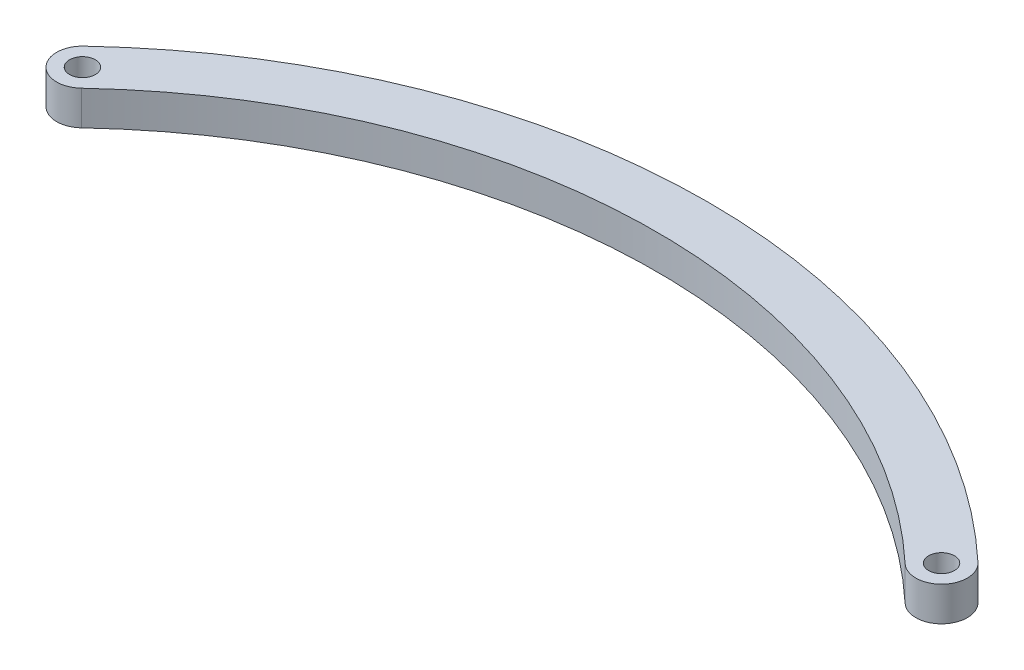
SolidWorks part; units mm, degrees
ref_plane "Front Plane" through (0, 0, 0) normal (0, 0, 1) x (1, 0, 0)
ref_plane "Top Plane" through (0, 0, 0) normal (0, 1, 0) x (1, 0, 0)
ref_plane "Right Plane" through (0, 0, 0) normal (1, 0, 0) x (0, 0, -1)
sketch "Esquisse1" plane through (0, 0, 0) normal (0, 1, 0) x (1, 0, 0)
  line L0 (-50, 0) -> (0, 0) construction
  line L1 (0, 0) -> (50, 0) construction
  circle A0 centre (-50, 0) radius 1.5
  circle A1 centre (50, 0) radius 1.5
  circle A2 centre (-50, 0) radius 3
  circle A3 centre (50, 0) radius 3
  circle A4 centre (0, -53.1883) radius 70
  circle A5 centre (0, -53.1883) radius 76
  dimension "D2" = 3
  dimension "D3" = 6
  dimension "D4" = 140
  dimension "D5" = 152
  dimension "D1" = 50
extrude "Boss.-Extru.1" add sketch "Esquisse1" along normal blind 4 contours A3 A5 A2 A4 | A2 A0 | A3 A1 region at (-47.3243, 0, 1.157) region at (-48.3843, 0, -3.7363) region at (52.6757, 0, -1.157)
